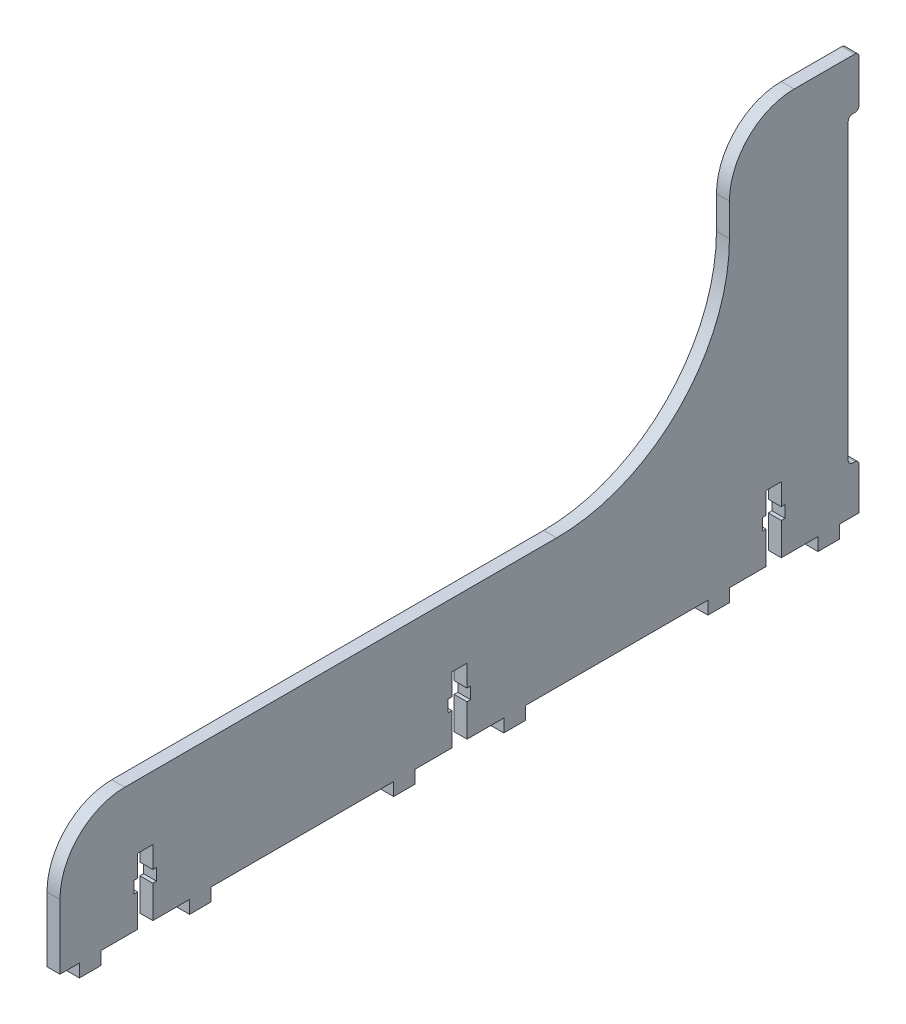
SolidWorks part; units mm, degrees
ref_plane "Front Plane" through (0, 0, 0) normal (0, 0, 1) x (1, 0, 0)
ref_plane "Top Plane" through (0, 0, 0) normal (0, 1, 0) x (1, 0, 0)
ref_plane "Right Plane" through (0, 0, 0) normal (1, 0, 0) x (0, 0, -1)
sketch "Sketch1" plane through (0, 0, 0) normal (1, 0, 0) x (0, 0, -1)
  line L0 (-185, -92.5) -> (185, 92.5) construction
  line L1 (183, 92.5) -> (155, 92.5)
  line L2 (-185, -92.5) -> (-185, -62.5)
  line L3 (-185, -92.5) -> (-176, -92.5)
  line L4 (185, -92.5) -> (185, -73)
  line L5 (0, -32.5) -> (0, -92.5) construction
  line L6 (149, -92.5) -> (149, -77.5)
  line L7 (149, -77.5) -> (150.7, -77.5)
  line L8 (150.7, -77.5) -> (150.7, -72)
  line L9 (150.7, -72) -> (149, -72)
  line L10 (149, -72) -> (149, -62)
  line L11 (149, -62) -> (142, -62)
  line L12 (142, -62) -> (142, -72)
  line L13 (142, -72) -> (140.3, -72)
  line L14 (140.3, -72) -> (140.3, -77.5)
  line L15 (140.3, -77.5) -> (142, -77.5)
  line L16 (142, -77.5) -> (142, -92.5)
  line L17 (166, -92.5) -> (166, -98.5)
  line L18 (166, -98.5) -> (176, -98.5)
  line L19 (176, -98.5) -> (176, -92.5)
  line L20 (115, -92.5) -> (115, -98.5)
  line L21 (115, -98.5) -> (125, -98.5)
  line L22 (125, -98.5) -> (125, -92.5)
  line L23 (30.5, -92.5) -> (30.5, -98.5)
  line L24 (30.5, -98.5) -> (20.5, -98.5)
  line L25 (20.5, -98.5) -> (20.5, -92.5)
  line L26 (-20.5, -92.5) -> (-20.5, -98.5)
  line L27 (-20.5, -98.5) -> (-30.5, -98.5)
  line L28 (-30.5, -98.5) -> (-30.5, -92.5)
  line L29 (-115, -92.5) -> (-115, -98.5)
  line L30 (-115, -98.5) -> (-125, -98.5)
  line L31 (-125, -98.5) -> (-125, -92.5)
  line L32 (-176, -92.5) -> (-176, -98.5)
  line L33 (-176, -98.5) -> (-166, -98.5)
  line L34 (-166, -98.5) -> (-166, -92.5)
  line L35 (166, -95.5) -> (125, -95.5) construction
  line L36 (115, -95.5) -> (30.5, -95.5) construction
  line L37 (20.5, -95.5) -> (-20.5, -95.5) construction
  line L38 (-30.5, -95.5) -> (-115, -95.5) construction
  line L39 (-125, -95.5) -> (-166, -95.5) construction
  line L40 (-166, -92.5) -> (-125, -92.5)
  line L41 (-115, -92.5) -> (-30.5, -92.5)
  line L42 (-20.5, -92.5) -> (20.5, -92.5)
  line L43 (30.5, -92.5) -> (115, -92.5)
  line L44 (125, -92.5) -> (166, -92.5)
  line L45 (145.5, -62) -> (145.5, -92.5) construction
  line L46 (176, -92.5) -> (185, -92.5)
  line L47 (72.75, -92.5) -> (72.75, -27.5329) construction
  line L48 (-3.5, -92.5) -> (-3.5, -77.5)
  line L49 (-3.5, -77.5) -> (-5.2, -77.5)
  line L50 (-5.2, -77.5) -> (-5.2, -72)
  line L51 (-5.2, -72) -> (-3.5, -72)
  line L52 (-3.5, -72) -> (-3.5, -62)
  line L53 (-3.5, -62) -> (3.5, -62)
  line L54 (3.5, -62) -> (3.5, -72)
  line L55 (3.5, -72) -> (5.2, -72)
  line L56 (5.2, -72) -> (5.2, -77.5)
  line L57 (5.2, -77.5) -> (3.5, -77.5)
  line L58 (3.5, -77.5) -> (3.5, -92.5)
  line L59 (-149, -92.5) -> (-149, -77.5)
  line L60 (-149, -77.5) -> (-150.7, -77.5)
  line L61 (-150.7, -77.5) -> (-150.7, -72)
  line L62 (-150.7, -72) -> (-149, -72)
  line L63 (-149, -72) -> (-149, -62)
  line L64 (-149, -62) -> (-142, -62)
  line L65 (-142, -62) -> (-142, -72)
  line L66 (-142, -72) -> (-140.3, -72)
  line L67 (-140.3, -72) -> (-140.3, -77.5)
  line L68 (-142, -77.5) -> (-142, -92.5)
  line L69 (-140.3, -77.5) -> (-142, -77.5)
  line L70 (183, -71) -> (182, -71)
  line L71 (-155, -32.5) -> (45, -32.5)
  line L72 (125, 47.5) -> (125, 62.5)
  line L73 (180, -69) -> (180, 67)
  line L74 (182, 69) -> (183, 69)
  line L75 (185, 71) -> (185, 90.5)
  arc A0 (125, 47.5) -> (45, -32.5) centre (45, 47.5) cw
  arc A1 (155, 92.5) -> (125, 62.5) centre (155, 62.5) ccw
  arc A2 (-155, -32.5) -> (-185, -62.5) centre (-155, -62.5) ccw
  arc A3 (185, 90.5) -> (183, 92.5) centre (183, 90.5) ccw
  arc A4 (185, 71) -> (183, 69) centre (183, 71) cw
  arc A5 (182, 69) -> (180, 67) centre (182, 67) ccw
  arc A6 (180, -69) -> (182, -71) centre (182, -69) ccw
  arc A7 (185, -73) -> (183, -71) centre (183, -73) ccw
  point P90 (-185, -32.5)
  point P104 (180, 69)
  point P107 (180, -71)
  point P110 (185, -71)
  dimension "D17" = 80
  dimension "D18" = 30
  dimension "D19" = 30
  dimension "D21" = 2
  dimension "D2" = 370
  dimension "D3" = 7
  dimension "D4" = 10
  dimension "D5" = 5.5
  dimension "D6" = 15
  dimension "D7" = 1.7
  dimension "D8" = 10
  dimension "D9" = 6
  dimension "D10" = 5
  dimension "D11" = 84.5
  dimension "D12" = 41
  dimension "D13" = 10.4
  dimension "D14" = 185
  dimension "D15" = 60
  dimension "D16" = 230
  dimension "D20" = 140
  dimension "D22" = 23.5
  dimension "D23" = 19.5
extrude "Boss-Extrude1" add sketch "Sketch1" along normal mid plane 6 contours L67 L69 L68 L40 L31 L30 L29 L41 L28 L27 L26 L42 L48 L49 L50 L51 L52 L53 L54 L55 L56 L57 L58 L25 L24 L23 L43 L20 L21 L22 L44 L16 L15 L14 L13 L12 L11 L10 L9 L8 L7 L6 L17 L18 L19 L46 region at (0, -39.5175, -40.1597)
